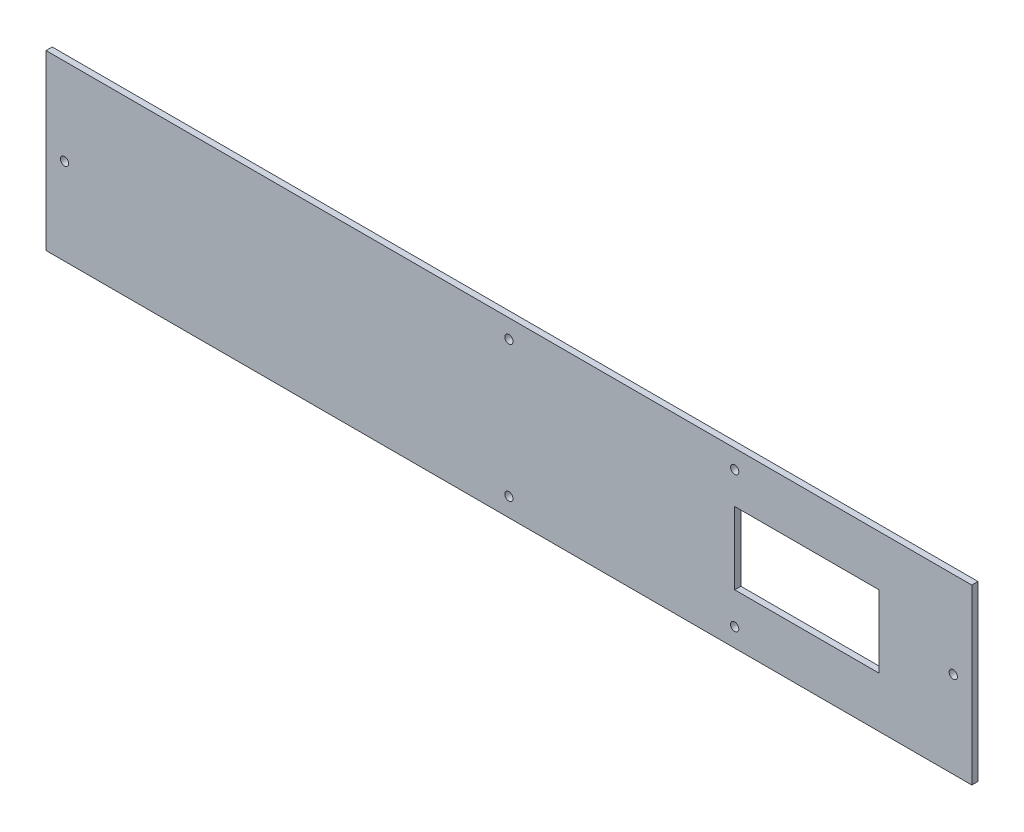
SolidWorks part; units mm, degrees
ref_plane "Piano frontale" through (0, 0, 0) normal (0, 0, 1) x (1, 0, 0)
ref_plane "Piano superiore" through (0, 0, 0) normal (0, 1, 0) x (1, 0, 0)
ref_plane "Piano destro" through (0, 0, 0) normal (1, 0, 0) x (0, 0, -1)
sketch "f" plane through (0, 0, 0) normal (0, 0, 1) x (1, 0, 0)
  line L0 (0, 0) -> (0, 84)
  line L1 (0, 84) -> (449, 84)
  line L2 (449, 84) -> (449, 0)
  line L3 (449, 0) -> (0, 0)
  line L4 (0, 42) -> (449, 42) construction
  line L5 (224.5, 42) -> (224.5, 123.488) construction
  line L6 (334, 59.5) -> (334, 24.5)
  line L7 (334, 24.5) -> (404, 24.5)
  line L8 (404, 24.5) -> (404, 59.5)
  line L9 (404, 59.5) -> (334, 59.5)
  line L10 (449, 84) -> (224.5, 0) construction
  line L11 (334, 42) -> (334, 84) construction
  circle A0 centre (9, 42) radius 2
  circle A1 centre (224.5, 75) radius 2
  circle A2 centre (224.5, 9) radius 2
  circle A3 centre (440, 42) radius 2
  circle A4 centre (334, 75) radius 2
  circle A5 centre (334, 9) radius 2
  dimension "D3" = 9
  dimension "D4" = 9
  dimension "D6" = 4
  dimension "D9" = 4
  dimension "D10" = 4
  dimension "D1" = 84
  dimension "D2" = 449
  dimension "D5" = 45
  dimension "D7" = 70
  dimension "D8" = 35
  dimension "D11" = 9
  dimension "D12" = 9
extrude "Estrusione-Estrusione1" add sketch "f" along normal blind 3
